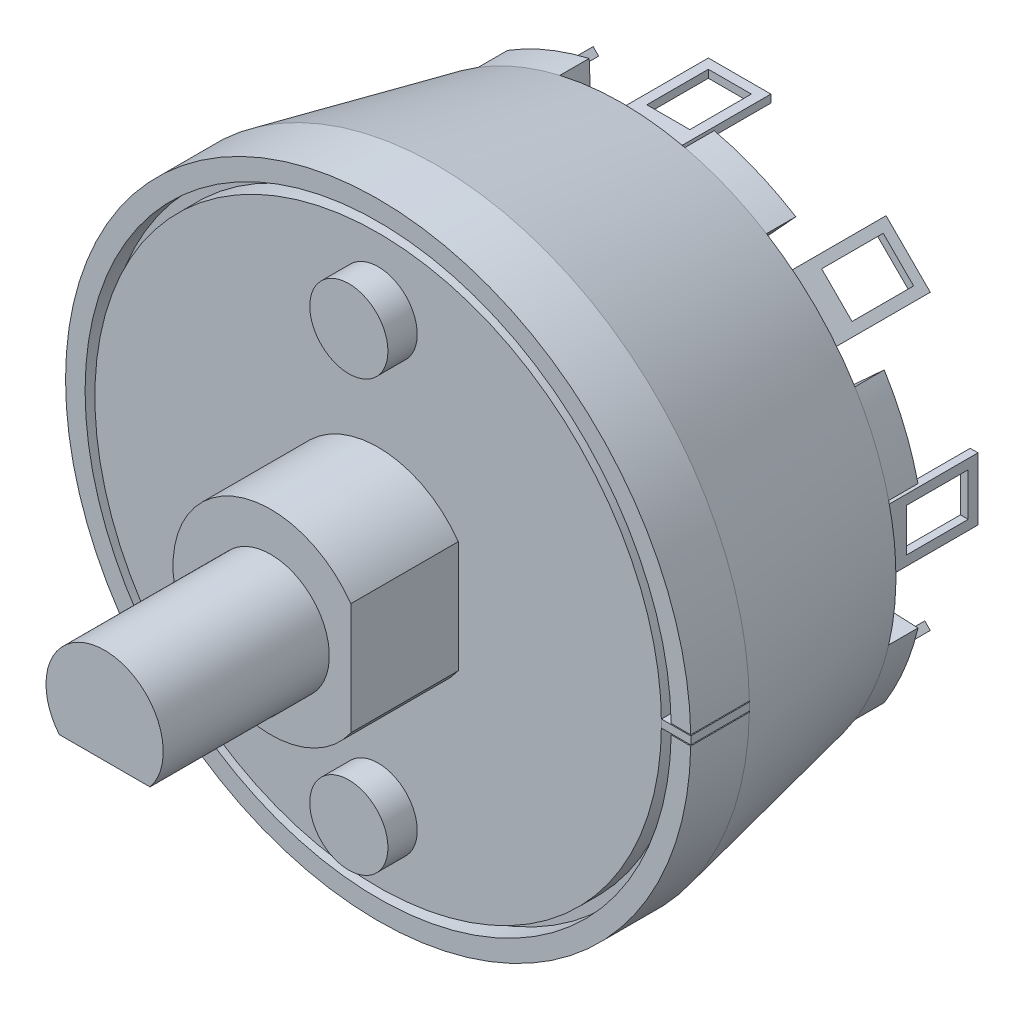
SolidWorks part; units mm, degrees
material "CA"
ref_plane "Alzado" through (0, 0, 0) normal (0, 0, 1) x (1, 0, 0)
ref_plane "Planta" through (0, 0, 0) normal (0, 1, 0) x (1, 0, 0)
ref_plane "Vista lateral" through (0, 0, 0) normal (1, 0, 0) x (0, 0, -1)
sketch "Croquis3" plane through (0, 0, 0) normal (1, 0, 0) x (0, 0, -1)
  line L0 (0, 0) -> (0, 3)
  line L1 (0, 55) -> (0, -55) construction
  line L2 (0, 3) -> (8.5, 3)
  line L3 (8.5, 3) -> (8.5, 5)
  line L4 (8.5, 5) -> (14, 5)
  line L5 (14, 5) -> (14, 16)
  line L6 (14, 16) -> (17, 16)
  line L7 (17, 16) -> (26.5, 14)
  line L8 (26.5, 14) -> (26.5, 0)
  line L9 (55, 0) -> (-55, 0) construction
  line L10 (26.5, 0) -> (0, 0)
  dimension "D1" = 8.5
  dimension "D2" = 5.5
  dimension "D3" = 3
  dimension "D4" = 5
  dimension "D5" = 16
  dimension "D6" = 3
  dimension "D7" = 12.5
  dimension "D8" = 14
revolve "Revolución1" add sketch "Croquis3" angle 360 about L10
sketch "Croquis4" plane through (0, 0, 0) normal (0, 0, 1) x (1, 0, 0)
  line L0 (-2.3216, -1.9) -> (2.3216, -1.9)
  circle A0 centre (0, 0) radius 3 construction
  arc A1 (-2.3216, -1.9) -> (2.3216, -1.9) centre (0, 0) ccw
  dimension "D1" = 1.9
extrude "Cortar-Extruir1" cut sketch "Croquis4" against normal blind 6.5
sketch "Croquis5" plane through (0, 0, -8.5) normal (0, 0, 1) x (1, 0, 0)
  line L0 (4.1, 2.8618) -> (4.1, -2.8618)
  circle A0 centre (0, 0) radius 5 construction
  circle A1 centre (0, 0) radius 5 construction
  arc A2 (4.1, -2.8618) -> (4.1, 2.8618) centre (0, 0) ccw
  dimension "D1" = 4.1
extrude "Cortar-Extruir2" cut sketch "Croquis5" against normal up to surface (5.5 mm away) up to face at (-5, 0, -14)
sketch "Croquis6" plane through (0, 0, -14) normal (0, 0, 1) x (1, 0, 0)
  circle A0 centre (0, 11) radius 2
  circle A1 centre (0, -11) radius 2
  dimension "D1" = 22
  dimension "D3" = 4
  dimension "D2" = 11
extrude "Saliente-Extruir1" add sketch "Croquis6" along normal blind 1.5
sketch "Croquis10" plane through (0, 0, -14) normal (0, 0, 1) x (1, 0, 0)
  circle A0 centre (0, 0) radius 14.5
  circle A1 centre (0, 0) radius 15
  dimension "D1" = 30
  dimension "D2" = 29
extrude "Cortar-Extruir5" cut sketch "Croquis10" against normal blind 1
sketch "Croquis11" plane through (0, 0, -14) normal (0, 0, 1) x (1, 0, 0)
  line L1 (14.5, -0.25) -> (16, -0.25)
  line L2 (14.5, -0.25) -> (14.5, 0.25)
  line L3 (14.5, 0.25) -> (16, 0.25)
  line L4 (16, -0.25) -> (16, 0.25)
  line L5 (14.5, -0.25) -> (16, 0.25) construction
  line L6 (14.5, 0.25) -> (16, -0.25) construction
  circle A0 centre (0, 0) radius 16 construction
  circle A1 centre (0, 0) radius 14.5 construction
  circle A2 centre (0, 0) radius 16
  circle A3 centre (0, 0) radius 14.5
  point P0 (15.25, 0)
  dimension "D1" = 0.5
extrude "Cortar-Extruir6" cut sketch "Croquis11" against normal blind 3 contours A2 L3 L2 L1 region at (15.2497, 0, -14)
sketch "Croquis12" plane through (0, 0, -14) normal (0, 0, 1) x (1, 0, 0)
  line L1 (14.5, -0.1994) -> (15.9987, -0.1994)
  line L2 (14.5, -0.1994) -> (14.5, 0.2006)
  line L3 (14.5, 0.2006) -> (15.9987, 0.2006)
  line L4 (15.9987, -0.1994) -> (15.9987, 0.2006)
  line L5 (14.5, -0.1994) -> (15.9987, 0.2006) construction
  line L6 (14.5, 0.2006) -> (15.9987, -0.1994) construction
  arc A0 (15.998, -0.25) -> (15.998, 0.25) centre (0, 0) ccw construction
  circle A1 centre (0, 0) radius 14.5 construction
  circle A2 centre (0, 0) radius 14.5
  point P0 (15.2494, 0.0006)
  dimension "D1" = 0.4
extrude "Saliente-Extruir5" add sketch "Croquis12" against normal blind 3 separate body contours L1 L4 L3 L2 region at (15.2494, 0.0006, -14)
sketch "Croquis13" plane through (0, 0, -26.5) normal (0, 0, -1) x (-1, 0, 0)
  line L0 (-1000, 0) -> (49000, 0) construction
  line L1 (0, -1000) -> (0, 49000) construction
  line L2 (0, 0) -> (-35355.3391, 35355.3391) construction
  line L3 (-3.2, 13.6294) -> (-3.0211, 9.5327)
  line L4 (-12.2, -1.6) -> (-11.8, -1.6)
  line L5 (-12.2, -1.6) -> (-12.2, 1.6)
  line L6 (-12.2, 1.6) -> (-11.8, 1.6)
  line L7 (-7.3747, 11.9002) -> (-4.6044, 8.8769)
  line L8 (0, 0) -> (-46193.9766, 19134.1716) construction
  line L9 (-11.9002, 7.3747) -> (-8.8769, 4.6044)
  line L10 (-13.6294, 3.2) -> (-9.5327, 3.0211)
  line L11 (-14, 0) -> (-10, 0)
  line L12 (-11.8, -1.6) -> (-11.8, 1.6)
  line L13 (-12.2, -1.6) -> (-11.8, 1.6) construction
  line L14 (-12.2, 1.6) -> (-11.8, -1.6) construction
  line L15 (-9.4752, 7.2125) -> (-7.2125, 9.4752)
  line L16 (-7.4953, 9.7581) -> (-7.2125, 9.4752)
  line L17 (-9.7581, 7.4953) -> (-7.4953, 9.7581)
  line L18 (-9.7581, 7.4953) -> (-9.4752, 7.2125)
  line L19 (7.3747, 11.9002) -> (4.6044, 8.8769)
  line L20 (3.2, 13.6294) -> (3.0211, 9.5327)
  line L21 (-1.6, 11.8) -> (1.6, 11.8)
  line L22 (1.6, 12.2) -> (1.6, 11.8)
  line L23 (-1.6, 12.2) -> (1.6, 12.2)
  line L24 (-1.6, 12.2) -> (-1.6, 11.8)
  line L25 (13.6294, 3.2) -> (9.5327, 3.0211)
  line L26 (11.9002, 7.3747) -> (8.8769, 4.6044)
  line L27 (7.2125, 9.4752) -> (9.4752, 7.2125)
  line L28 (9.7581, 7.4953) -> (9.4752, 7.2125)
  line L29 (7.4953, 9.7581) -> (9.7581, 7.4953)
  line L30 (7.4953, 9.7581) -> (7.2125, 9.4752)
  line L31 (11.9002, -7.3747) -> (8.8769, -4.6044)
  line L32 (13.6294, -3.2) -> (9.5327, -3.0211)
  line L33 (11.8, 1.6) -> (11.8, -1.6)
  line L34 (12.2, -1.6) -> (11.8, -1.6)
  line L35 (12.2, 1.6) -> (12.2, -1.6)
  line L36 (12.2, 1.6) -> (11.8, 1.6)
  line L37 (3.2, -13.6294) -> (3.0211, -9.5327)
  line L38 (7.3747, -11.9002) -> (4.6044, -8.8769)
  line L39 (9.4752, -7.2125) -> (7.2125, -9.4752)
  line L40 (7.4953, -9.7581) -> (7.2125, -9.4752)
  line L41 (9.7581, -7.4953) -> (7.4953, -9.7581)
  line L42 (9.7581, -7.4953) -> (9.4752, -7.2125)
  line L43 (-7.3747, -11.9002) -> (-4.6044, -8.8769)
  line L44 (-3.2, -13.6294) -> (-3.0211, -9.5327)
  line L45 (1.6, -11.8) -> (-1.6, -11.8)
  line L46 (-1.6, -12.2) -> (-1.6, -11.8)
  line L47 (1.6, -12.2) -> (-1.6, -12.2)
  line L48 (1.6, -12.2) -> (1.6, -11.8)
  line L49 (-13.6294, -3.2) -> (-9.5327, -3.0211)
  line L50 (-11.9002, -7.3747) -> (-8.8769, -4.6044)
  line L51 (-7.2125, -9.4752) -> (-9.4752, -7.2125)
  line L52 (-9.7581, -7.4953) -> (-9.4752, -7.2125)
  line L53 (-7.4953, -9.7581) -> (-9.7581, -7.4953)
  line L54 (-7.4953, -9.7581) -> (-7.2125, -9.4752)
  circle A0 centre (0, 0) radius 10
  circle A1 centre (0, 0) radius 14 construction
  arc A2 (-11.9002, 7.3747) -> (-13.6294, 3.2) centre (0, 0) ccw
  arc A3 (-3.2, 13.6294) -> (-7.3747, 11.9002) centre (0, 0) ccw
  arc A4 (7.3747, 11.9002) -> (3.2, 13.6294) centre (0, 0) ccw
  arc A5 (13.6294, 3.2) -> (11.9002, 7.3747) centre (0, 0) ccw
  arc A6 (11.9002, -7.3747) -> (13.6294, -3.2) centre (0, 0) ccw
  arc A7 (3.2, -13.6294) -> (7.3747, -11.9002) centre (0, 0) ccw
  arc A8 (-7.3747, -11.9002) -> (-3.2, -13.6294) centre (0, 0) ccw
  arc A9 (-13.6294, -3.2) -> (-11.9002, -7.3747) centre (0, 0) ccw
  point P4 (-12, 0)
  point P83 (0, 0)
  circle M13 centre (0, 0) radius 14
  dimension "D1" = 20
  dimension "D2" = 45
  dimension "D3" = 22.5
  dimension "D4" = 20
  dimension "D5" = 20
  dimension "D6" = 3.2
  dimension "D7" = 3.2
  dimension "D8" = 0.4
  dimension "D9" = 8
extrude "Saliente-Extruir6" add sketch "Croquis13" along normal blind 1.5 contours A0 L19 L20 M13 | A0 L25 L26 M13 | A0 L31 L32 M13 | A0 L37 L38 M13 | A0 L43 L44 M13 | A0 L49 L50 M13 | A0 L9 L10 M13 | A0 L3 L7 M13 region at (4.6924, 11.3286, -26.5) region at (-4.6924, 11.3286, -26.5) region at (11.3286, 4.6924, -26.5) region at (-11.3286, 4.6924, -26.5) region at (11.3286, -4.6924, -26.5) region at (-11.3286, -4.6924, -26.5) region at (4.6924, -11.3286, -26.5) region at (-4.6924, -11.3286, -26.5)
extrude "Saliente-Extruir7" add sketch "Croquis13<3>" along normal blind 6 contours L23 L24 L21 L22 | L29 L30 L27 L28 | L17 L18 L15 L16 | L4 L12 L11 L5 | L11 L12 L6 L5 | L53 L54 L51 L52 | L47 L48 L45 L46 | L41 L42 L39 L40 | L35 L36 L33 L34 region at (12, -0.8, -26.5) region at (12, 0.8, -26.5) region at (8.4853, 8.4853, -26.5) region at (0, 12, -26.5) region at (-8.4853, 8.4853, -26.5) region at (-12, 0, -26.5) region at (-8.4853, -8.4853, -26.5) region at (0, -12, -26.5) region at (8.4853, -8.4853, -26.5)
sketch "Croquis13<3>" plane through (0, 0, -26.5) normal (0, 0, -1) x (-1, 0, 0) same geometry as "Croquis13"
sketch "Croquis14" plane through (0, 12.2, 0) normal (0, 1, 0) x (1, 0, 0)
  line L0 (1.6, 32.5) -> (-1.6, 32.5) construction
  line L1 (-1.1, 28.85) -> (1.1, 28.85)
  line L2 (-1.1, 28.85) -> (-1.1, 32)
  line L3 (-1.1, 32) -> (1.1, 32)
  line L4 (1.1, 28.85) -> (1.1, 32)
  line L5 (-1.1, 28.85) -> (1.1, 32) construction
  line L6 (-1.1, 32) -> (1.1, 28.85) construction
  point P0 (0, 30.425)
  point P8 (0, 32.5)
  dimension "D1" = 2.2
  dimension "D2" = 3.15
  dimension "D3" = 0.5
extrude "Cortar-Extruir8" cut sketch "Croquis14" against normal through all
sketch "Croquis15" plane through (-12.2, 0, 0) normal (-1, 0, 0) x (0, 0, 1)
  line L0 (-32.5, 1.6) -> (-32.5, -1.6) construction
  line L1 (-28.85, -1.1) -> (-32, -1.1)
  line L2 (-28.85, -1.1) -> (-28.85, 1.1)
  line L3 (-28.85, 1.1) -> (-32, 1.1)
  line L4 (-32, -1.1) -> (-32, 1.1)
  line L5 (-28.85, -1.1) -> (-32, 1.1) construction
  line L6 (-28.85, 1.1) -> (-32, -1.1) construction
  point P0 (-30.425, 0)
  point P8 (-32.5, 0)
  dimension "D1" = 3.15
  dimension "D2" = 2.2
  dimension "D3" = 0.5
sketch "Croquis16" plane through (-8.6267, 8.6267, 0) normal (-0.7071, 0.7071, 0) x (0, 0, 1)
  line L0 (-32.5, 1.6) -> (-32.5, -1.6) construction
  line L1 (-32, -1.1) -> (-28.85, -1.1)
  line L2 (-32, -1.1) -> (-32, 1.1)
  line L3 (-32, 1.1) -> (-28.85, 1.1)
  line L4 (-28.85, -1.1) -> (-28.85, 1.1)
  line L5 (-32, -1.1) -> (-28.85, 1.1) construction
  line L6 (-32, 1.1) -> (-28.85, -1.1) construction
  point P0 (-30.425, 0)
  point P7 (-32.5, 0)
  dimension "D1" = 0.5
  dimension "D2" = 3.15
  dimension "D3" = 2.2
extrude "Cortar-Extruir10" cut sketch "Croquis16" against normal through all
sketch "Croquis17" plane through (-8.6267, -8.6267, 0) normal (-0.7071, -0.7071, 0) x (0, 0, 1)
  line L0 (-32.5, 1.6) -> (-32.5, -1.6) construction
  line L1 (-32, -1.1) -> (-28.85, -1.1)
  line L2 (-32, -1.1) -> (-32, 1.1)
  line L3 (-32, 1.1) -> (-28.85, 1.1)
  line L4 (-28.85, -1.1) -> (-28.85, 1.1)
  line L5 (-32, -1.1) -> (-28.85, 1.1) construction
  line L6 (-32, 1.1) -> (-28.85, -1.1) construction
  point P0 (-30.425, 0)
  point P8 (-32.5, 0)
  dimension "D1" = 0.5
  dimension "D2" = 3.15
  dimension "D3" = 2.2
extrude "Cortar-Extruir11" cut sketch "Croquis17" against normal through all
sketch "Croquis18" plane through (0, 0, -26.5) normal (0, 0, -1) x (-1, 0, 0)
  line L1 (-0.2, -1.6) -> (0.2, -1.6)
  line L2 (-0.2, -1.6) -> (-0.2, 1.6)
  line L3 (-0.2, 1.6) -> (0.2, 1.6)
  line L4 (0.2, -1.6) -> (0.2, 1.6)
  line L5 (-0.2, -1.6) -> (0.2, 1.6) construction
  line L6 (-0.2, 1.6) -> (0.2, -1.6) construction
  point P0 (0, 0)
  dimension "D1" = 3.2
  dimension "D2" = 0.4
extrude "Saliente-Extruir8" add sketch "Croquis18" along normal blind 6
extrude "Cortar-Extruir12" cut sketch "Croquis15" against normal through all
